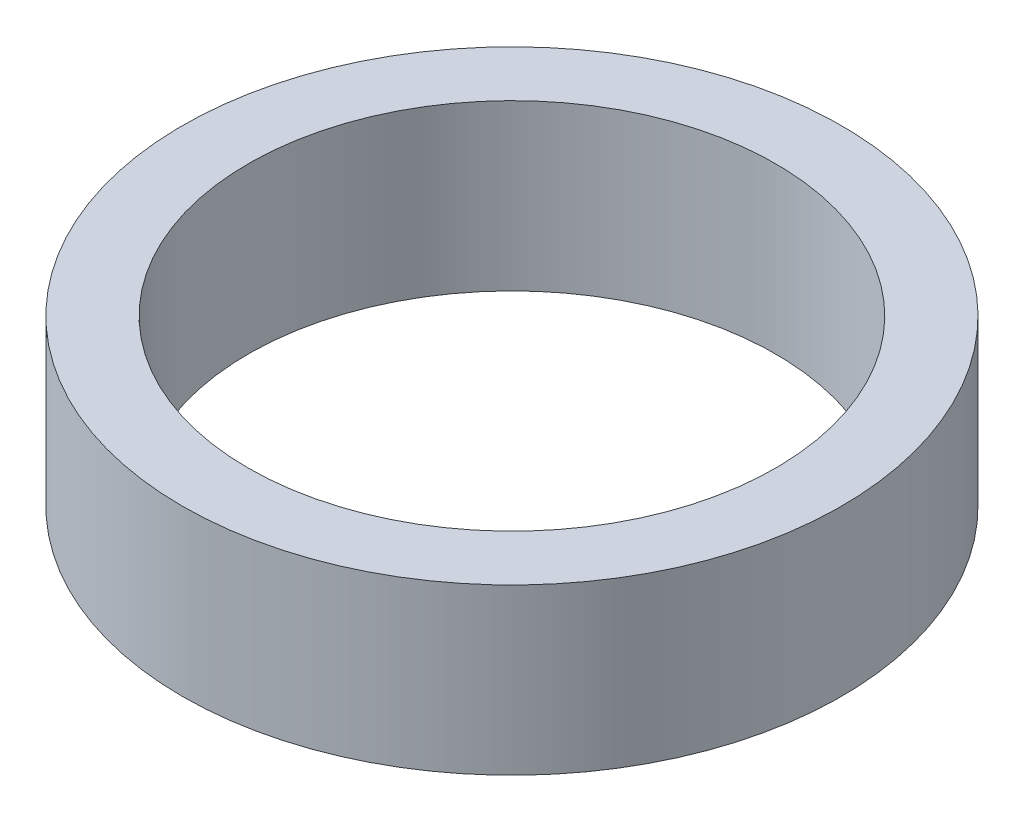
SolidWorks part; units mm, degrees
ref_plane "Front Plane" through (0, 0, 0) normal (0, 0, 1) x (1, 0, 0)
ref_plane "Top Plane" through (0, 0, 0) normal (0, 1, 0) x (1, 0, 0)
ref_plane "Right Plane" through (0, 0, 0) normal (1, 0, 0) x (0, 0, -1)
sketch "Sketch1" plane through (0, 0, 0) normal (0, 1, 0) x (1, 0, 0)
  circle A0 centre (0, 0) radius 50
  dimension "FLANGE_OD" = 100
extrude "Boss-Extrude1" add sketch "Sketch1" along normal blind 25
sketch "Sketch2" plane through (0, 0, 0) normal (0, 1, 0) x (1, 0, 0)
  circle A0 centre (0, 0) radius 40
  dimension "BORE_D" = 80
extrude "Cut-Extrude1" cut sketch "Sketch2" along normal through all
sketch "Sketch3" plane through (0, 25, 0) normal (0, 1, 0) x (1, 0, 0)
  circle A0 centre (0, 0) radius 22.3014 construction
  circle A1 centre (-22.3014, 0) radius 1.5842
  dimension "BOLT_D" = 3.1683
  dimension "BOLT_PCD" = 44.6028
extrude "Cut-Extrude2" cut sketch "Sketch3" against normal blind 19.4663 rebuild error yes
pattern_circular "CirPattern1" count 8 over 360 rebuild error yes
